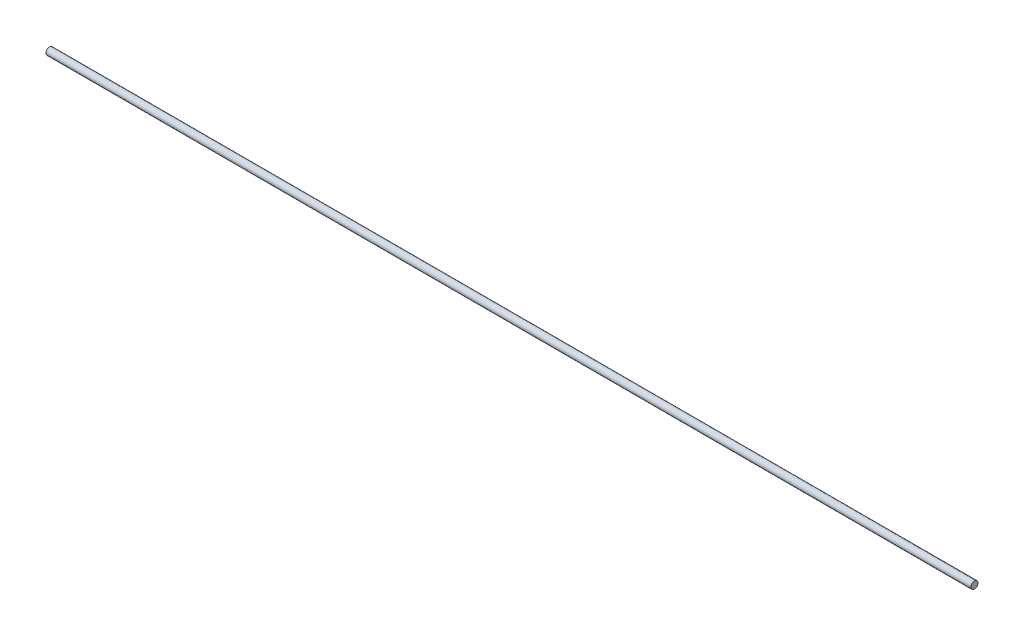
SolidWorks part; units mm, degrees
material "Hexcel AS4C (3000 Filaments)"
ref_plane "Front Plane" through (0, 0, 0) normal (0, 0, 1) x (1, 0, 0)
ref_plane "Top Plane" through (0, 0, 0) normal (0, 1, 0) x (1, 0, 0)
ref_plane "Right Plane" through (0, 0, 0) normal (1, 0, 0) x (0, 0, -1)
sketch "Sketch1" plane through (0, 0, 0) normal (1, 0, 0) x (0, 0, -1)
  circle A1 centre (0, 0) radius 3.1369
  dimension "D1" = 6.2738
extrude "Boss-Extrude1" add sketch "Sketch1" along normal blind 812.8 contours A1
